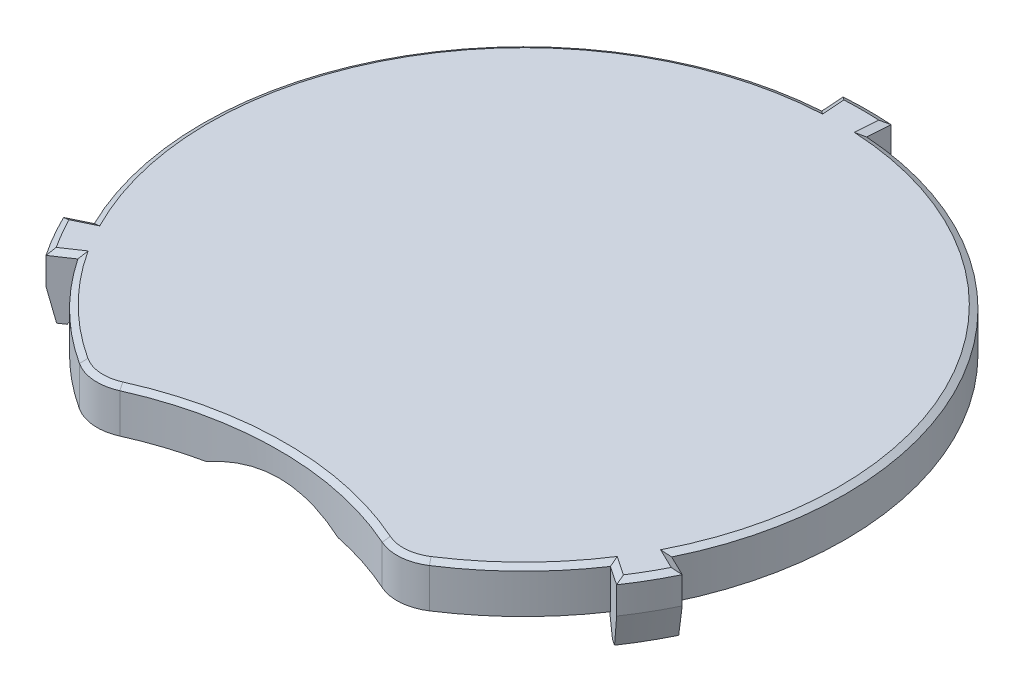
SolidWorks part; units mm, degrees
ref_plane "Спереди" through (0, 0, 0) normal (0, 0, 1) x (1, 0, 0)
ref_plane "Сверху" through (0, 0, 0) normal (0, 1, 0) x (1, 0, 0)
ref_plane "Справа" through (0, 0, 0) normal (1, 0, 0) x (0, 0, -1)
sketch "Эскиз2" plane through (0, 0, 0) normal (0, 0, 1) x (1, 0, 0)
  line L0 (0, 0) -> (0, -0.8)
  line L1 (0, 0) -> (-21, 0)
  line L2 (-21, 0) -> (-21, -2.8)
  line L3 (-21, -2.8) -> (-17, -2.8)
  line L4 (-17, -2.8) -> (-15, -0.8)
  line L5 (-15, -0.8) -> (0, -0.8)
  line L6 (0, 0) -> (0, 6.0023) construction
  line L7 (-21, -2.8) -> (-22.5, -2.8) construction
  line L9 (-22.5, -1.5) -> (-22.5, -4) construction
  point P1 (-16.2025, -2.8)
  point P10 (0, 0)
  point P11 (-22.2192, -2.8)
  point P12 (-22.5, -2.8)
  point P13 (-21.9147, -2.8)
  point P14 (0, 0)
  point P15 (-21.8433, -2.8)
  dimension "D1" = 1.5
  dimension "D2" = 0.8
  dimension "D3" = 2
  dimension "D4" = 15
  dimension "D5" = 45
revolve "Повернуть1" add sketch "Эскиз2" angle 360 about L6
sketch "Эскиз3" plane through (0, 0, 0) normal (1, 0, 0) x (0, 0, -1)
  line L0 (0, 0) -> (21, 0) construction
  line L1 (21, 0) -> (22.5, 0)
  line L2 (22.5, 0) -> (22.5, -2)
  line L4 (22, -4) -> (21.5, -4)
  line L5 (21.5, -4) -> (19, 0)
  line L7 (21, 0) -> (19, 0)
  line L8 (0, 0) -> (0, -5.1786) construction
  line L9 (22.5, -2) -> (22, -4)
  line L10 (22.5, -4) -> (22.5, -1.5) construction
  point P5 (22.5, -4)
  point P6 (22.5, -5)
  point P7 (22.0758, -3)
  point P10 (19, -3.2339)
  point P15 (0, 0)
  point P17 (22.5, -3)
  point P20 (19, 0.3301)
  point P21 (19, -0.1003)
  dimension "D1" = 4
  dimension "D3" = 2
  dimension "D4" = 2
  dimension "D5" = 1
  dimension "D6" = 0.5
revolve "Повернуть2" add sketch "Эскиз3" angle 8 mid plane about L8
pattern_circular "Круговой массив1" count 3 over 360 about axis through (0, 0, 0) along (0, 1, 0) of "Повернуть2"
sketch "Эскиз4" plane through (0, 0, 0) normal (0, 1, 0) x (1, 0, 0)
  line L0 (0, 0) -> (0, -21) construction
  circle A0 centre (0, -37) radius 21
  circle A1 centre (0, 0) radius 21 construction
  point P2 (0, -14.0727)
  point P9 (0, -16)
  point P10 (0, -13)
  point P11 (0, -34)
  dimension "D1" = 5
extrude "Вырез-Вытянуть1" cut sketch "Эскиз4" against normal through all
fillet "Скругление1" radius 3 2 edges at (9.9373, -1.4, 18.5) (-9.9373, -1.4, 18.5)
chamfer "Фаска1" distance 0.4 angle 30 16 edges at (1.5172, 0, -21.697) (-1.5172, 0, -21.697) (0, 0, -22.5) (14.7202, 0, 14.9772) (18.0316, 0, 12.1624) (19.5488, 0, 9.5346) (19.4856, 0, 11.25) (-18.1865, 0, -10.5) (-19.5488, 0, 9.5346) (-18.0316, 0, 12.1624) (-19.4856, 0, 11.25) (18.1865, 0, -10.5) (0, 0, 16) (-14.7202, 0, 14.9772) (-10.0384, 0, 18.0856) (10.0384, 0, 18.0856)
